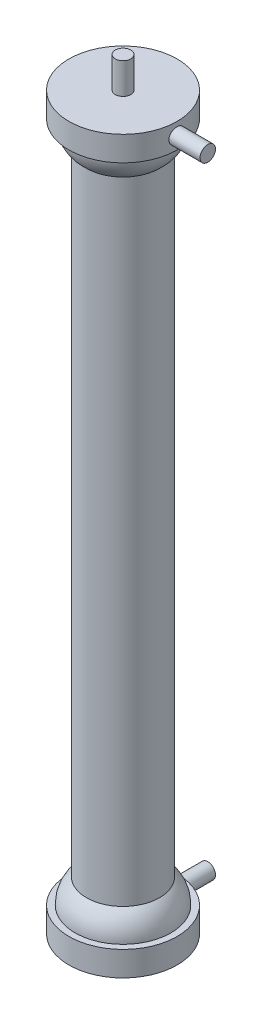
SolidWorks part; units mm, degrees
ref_plane "Front Plane" through (0, 0, 0) normal (0, 0, 1) x (1, 0, 0)
ref_plane "Top Plane" through (0, 0, 0) normal (0, 1, 0) x (1, 0, 0)
ref_plane "Right Plane" through (0, 0, 0) normal (1, 0, 0) x (0, 0, -1)
sketch "Sketch1" plane through (0, 0, 0) normal (0, 0, 1) x (1, 0, 0)
  line L1 (15, 33.02) -> (15, 292.38)
  line L4 (0, -1025.4) -> (0, 0) construction
  line L5 (19.685, 302.54) -> (22.225, 302.54)
  line L6 (22.225, 302.54) -> (22.225, 312.7)
  line L7 (19.685, 22.86) -> (22.225, 22.86)
  line L8 (22.225, 22.86) -> (22.225, 12.7)
  line L9 (3.175, 12.7) -> (22.225, 12.7)
  line L10 (3.175, 312.7) -> (22.225, 312.7)
  line L11 (3.175, 12.7) -> (3.175, 0)
  line L12 (3.175, 0) -> (0, 0)
  line L14 (0, -1333.3322) -> (0, 0) construction
  line L15 (3.175, 312.7) -> (3.175, 325.4)
  line L16 (3.175, 325.4) -> (0, 325.4)
  line L18 (0, 325.4) -> (0, 50000) construction
  line L20 (0, 325.4) -> (0, 0)
  arc A0 (19.685, 22.86) -> (15, 33.02) centre (6.9887, 23.1656) ccw
  arc A1 (19.685, 302.54) -> (15, 292.38) centre (6.9887, 302.2344) cw
  dimension "D5" = 12.7
  dimension "D7" = 2.54
  dimension "D1" = 44.45
  dimension "D2" = 30
  dimension "D3" = 300
  dimension "D4" = 10.16
  dimension "D6" = 10.16
  dimension "D8" = 10.16
  dimension "D9" = 12.7
  dimension "D10" = 6.35
revolve "Revolve1" add sketch "Sketch1" angle 360 about L4
sketch "Sketch2" plane through (0, 0, 0) normal (1, 0, 0) x (0, 0, -1)
  line L0 (0, 312.7) -> (0, 302.54) construction
  line L1 (22.225, 312.7) -> (-22.225, 312.7) construction
  line L2 (-19.685, 302.54) -> (19.685, 302.54) construction
  circle A0 centre (0, 307.62) radius 3.175
  point P9 (0, 307.62)
  dimension "D1" = 6.35
extrude "Boss-Extrude1" add sketch "Sketch2" along normal blind 34.798
sketch "Sketch3" plane through (0, 0, 0) normal (0, 0, 1) x (1, 0, 0)
  line L0 (0, 12.7) -> (0, 22.86) construction
  line L1 (-3.175, 12.7) -> (3.175, 12.7) construction
  line L2 (22.225, 22.86) -> (-22.225, 22.86) construction
  circle A0 centre (0, 17.78) radius 3.175
  point P9 (0, 17.78)
  dimension "D1" = 6.35
extrude "Boss-Extrude2" add sketch "Sketch3" against normal blind 34.798
